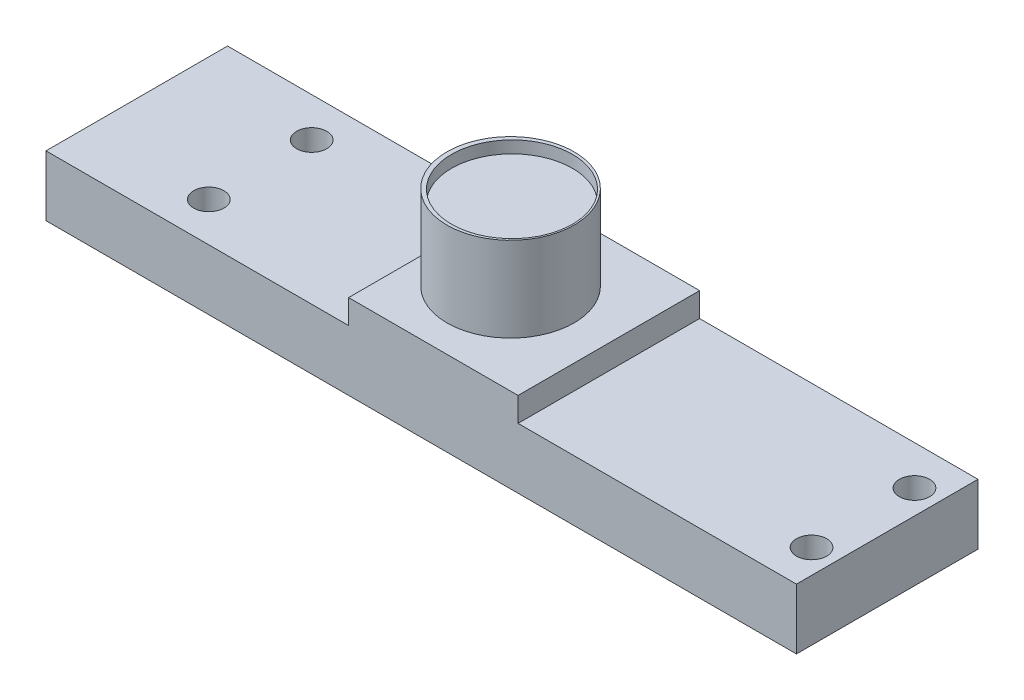
SolidWorks part; units mm, degrees
material "Aluminum Bronze"
ref_plane "Front Plane" through (0, 0, 0) normal (0, 0, 1) x (1, 0, 0)
ref_plane "Top Plane" through (0, 0, 0) normal (0, 1, 0) x (1, 0, 0)
ref_plane "Right Plane" through (0, 0, 0) normal (1, 0, 0) x (0, 0, -1)
sketch "Sketch1" plane through (0, 0, 0) normal (0, 1, 0) x (1, 0, 0)
  line L0 (31, -4.25) -> (29, -4.25) construction
  line L1 (-31, 7.5) -> (31, 7.5)
  line L2 (-31, 7.5) -> (-31, -7.5)
  line L3 (-31, -7.5) -> (31, -7.5)
  line L4 (31, 7.5) -> (31, -7.5)
  line L5 (-31, 7.5) -> (31, -7.5) construction
  line L6 (-31, -7.5) -> (31, 7.5) construction
  line L7 (31, 4.25) -> (29, 4.25) construction
  line L8 (-31, 4.25) -> (-20.8, 4.25) construction
  line L9 (-31, -4.25) -> (-20.8, -4.25) construction
  line L10 (-31, 0) -> (-0.12, 0) construction
  line L11 (-6, 7.5) -> (-6, -7.5)
  line L12 (-6, -7.5) -> (8, -7.5)
  line L13 (8, -7.5) -> (8, 7.5)
  line L14 (8, 7.5) -> (-6, 7.5)
  circle A0 centre (29, 4.25) radius 1.25
  circle A1 centre (29, -4.25) radius 1.25
  circle A2 centre (-20.8, 4.25) radius 1.25
  circle A3 centre (-20.8, -4.25) radius 1.25
  circle A4 centre (-0.12, 0) radius 5.25
  point P0 (0, 0)
  dimension "D7" = 2.5
  dimension "D13" = 10.5
  dimension "D1" = 62
  dimension "D2" = 3.25
  dimension "D3" = 2
  dimension "D4" = 15
  dimension "D5" = 3.25
  dimension "D6" = 2
  dimension "D8" = 3.25
  dimension "D9" = 10.2
  dimension "D10" = 10.2
  dimension "D11" = 3.25
  dimension "D12" = 30.88
  dimension "D14" = 14
  dimension "D15" = 25
extrude "Boss-Extrude1" add sketch "Sketch1" along normal blind 5 contours L2 L1 L4 L3 | A4
extrude "Cut-Extrude1" cut sketch "Sketch1<7>" along normal blind 5 contours A2 | A3 | A1 | A0
sketch "Sketch1<7>" plane through (0, 0, 0) normal (0, 1, 0) x (1, 0, 0) same geometry as "Sketch1"
extrude "Boss-Extrude2" add sketch "Sketch1<8>" along normal blind 7 contours L11 L12 L13 L14
sketch "Sketch1<8>" plane through (0, 0, 0) normal (0, 1, 0) x (1, 0, 0) same geometry as "Sketch1"
extrude "Boss-Extrude3" add sketch "Sketch1<9>" along normal blind 14 contours A4
sketch "Sketch1<9>" plane through (0, 0, 0) normal (0, 1, 0) x (1, 0, 0) same geometry as "Sketch1"
sketch "Sketch2" plane through (0, 14, 0) normal (0, 1, 0) x (1, 0, 0)
  circle A0 centre (0, 0) radius 5
  dimension "D1" = 10
extrude "Cut-Extrude2" cut sketch "Sketch2" against normal blind 1
sketch "Sketch3" plane through (-31, 0, 0) normal (-1, 0, 0) x (0, 0, 1)
  line L0 (-7.5, 2.5) -> (0, 2.5) construction
  line L1 (-7.5, 5) -> (-7.5, 0) construction
  line L3 (-6, 4.75) -> (6, 4.75)
  line L4 (-6, 4.75) -> (-6, 0.25)
  line L5 (-6, 0.25) -> (6, 0.25)
  line L6 (6, 4.75) -> (6, 0.25)
  line L7 (-6, 4.75) -> (6, 0.25) construction
  line L8 (-6, 0.25) -> (6, 4.75) construction
  dimension "D1" = 12
  dimension "D2" = 4.5
  dimension "D3" = 7.5
extrude "Cut-Extrude4" cut sketch "Sketch3" against normal blind 8
ref_plane "Plane1" through (0, 18, 0) normal (0, 1, 0) x (1, 0, 0)
